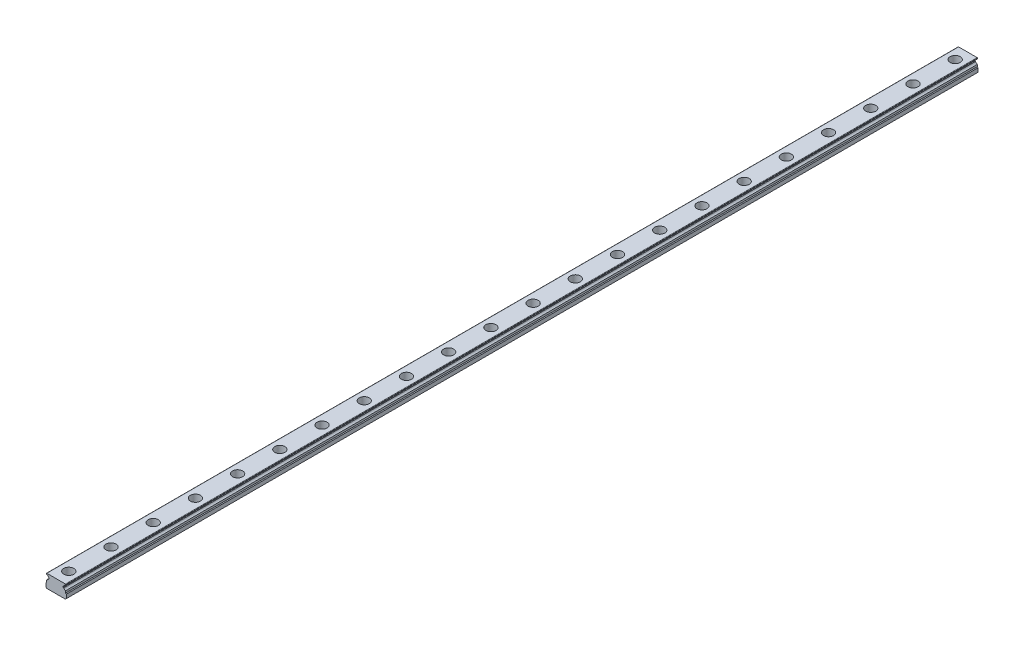
SolidWorks part; units mm, degrees
ref_plane "Front Plane" through (0, 0, 0) normal (0, 0, 1) x (1, 0, 0)
ref_plane "Top Plane" through (0, 0, 0) normal (0, 1, 0) x (1, 0, 0)
ref_plane "Right Plane" through (0, 0, 0) normal (1, 0, 0) x (0, 0, -1)
ref_plane "Plane1" through (0, 0, -595) normal (0, 0, -1) x (-1, 0, 0)
sketch "Sketch1" plane through (0, 0, -595) normal (0, 0, -1) x (-1, 0, 0)
  line L0 (5.6712, 7.2229) -> (5.7415, 7.4853)
  line L1 (5.5, 7.8) -> (-5.5, 7.8)
  line L2 (-5.7415, 7.4853) -> (-5.6712, 7.2229)
  line L3 (-4.5563, 6.2) -> (-4.1, 6.1195)
  line L4 (-4.1, 6.1195) -> (-4.1, 5.4805)
  line L5 (-4.1, 5.4805) -> (-6, 5.1454)
  line L6 (-6, 5.1454) -> (-6, 0)
  line L7 (-6, 0) -> (6, 0)
  line L8 (6, 0) -> (6, 2.8)
  line L9 (6, 2.8) -> (5.6, 3.2)
  line L10 (5.6, 3.2) -> (5.6, 4.3929)
  arc A0 (5.6, 4.3929) -> (5.6712, 7.2229) centre (5.95, 5.8) cw
  arc A1 (5.7415, 7.4853) -> (5.5, 7.8) centre (5.5, 7.55) ccw
  arc A2 (-5.5, 7.8) -> (-5.7415, 7.4853) centre (-5.5, 7.55) ccw
  arc A3 (-5.6712, 7.2229) -> (-4.5563, 6.2) centre (-5.95, 5.8) cw
extrude "Boss-Extrude1" add sketch "Sketch1" against normal blind 540
sketch "Sketch2" plane through (0, 0, -55) normal (0, 0, 1) x (1, 0, 0)
  line L0 (5.6, 5.216) -> (5.6, 3.2)
  line L1 (5.6, 3.2) -> (6, 2.8)
  line L2 (6, 2.8) -> (6, 5.1454)
  line L3 (6, 5.1454) -> (5.6, 5.216)
extrude "Cut-Extrude1" cut sketch "Sketch2" against normal through all
sketch "Sketch3" plane through (0, 0, -55) normal (0, 0, 1) x (1, 0, 0)
  line L0 (5.6, 5.216) -> (4.5563, 5.4)
  line L1 (5.6, 4.3929) -> (5.6, 5.216)
  arc A0 (4.5563, 5.4) -> (5.6, 4.3929) centre (5.95, 5.8) ccw
extrude "Cut-Extrude2" cut sketch "Sketch3" against normal through all
sketch "Sketch4" plane through (0, 0, -55) normal (0, 0, 1) x (1, 0, 0)
  line L0 (-4.5563, 5.4) -> (-4.1, 5.4805)
  line L1 (-4.1, 5.4805) -> (-4.1, 6.1195)
  line L2 (-4.1, 6.1195) -> (-4.5563, 6.2)
  arc A0 (-4.5563, 6.2) -> (-4.5563, 5.4) centre (-5.95, 5.8) cw
extrude "Cut-Extrude3" cut sketch "Sketch4" against normal blind 595
hole_wizard "CBORE for M3 Hex Head Machine Screw1" positions "Sketch6" profile "Sketch5" counterbore size "M3" standard "ANSI Metric"
sketch "Sketch6" plane through (0, 7.8, 0) normal (0, 1, 0) x (1, 0, 0)
  point P0 (0, 587.5)
  point P38 (0, 562.5)
  point P39 (0, 537.5)
  point P40 (0, 512.5)
  point P41 (0, 487.5)
  point P42 (0, 462.5)
  point P43 (0, 437.5)
  point P44 (0, 412.5)
  point P45 (0, 387.5)
  point P46 (0, 362.5)
  point P47 (0, 337.5)
  point P48 (0, 312.5)
  point P49 (0, 287.5)
  point P50 (0, 262.5)
  point P51 (0, 237.5)
  point P52 (0, 212.5)
  point P53 (0, 187.5)
  point P54 (0, 162.5)
  point P55 (0, 137.5)
  point P56 (0, 112.5)
  point P57 (0, 87.5)
  point P58 (0, 62.5)
  dimension "D1" = 22
sketch "Sketch5" plane through (0, 7.8, -587.5) normal (1, 0, 0) x (0, 0, 1)
  line L0 (0, 0) -> (0, 7.8)
  line L1 (0, 7.8) -> (1.75, 7.8)
  line L3 (1.75, 7.8) -> (1.75, 4.8)
  line L4 (1.75, 4.8) -> (3, 4.8)
  line L5 (3, 4.8) -> (3, 0)
  line L7 (3, 0) -> (0, 0)
  line L11 (0, -6.35) -> (0, 107.95) construction
  dimension "Thru Hole Dia." = 3.5
  dimension "Thru Hole Depth" = 7.8
  dimension "C'Bore Dia." = 6
  dimension "C'Bore Depth" = 4.8
chamfer "Chamfer1" distance 0.5 angle 45 2 edges at (-6, 0, -325) (6, 0, -325)
